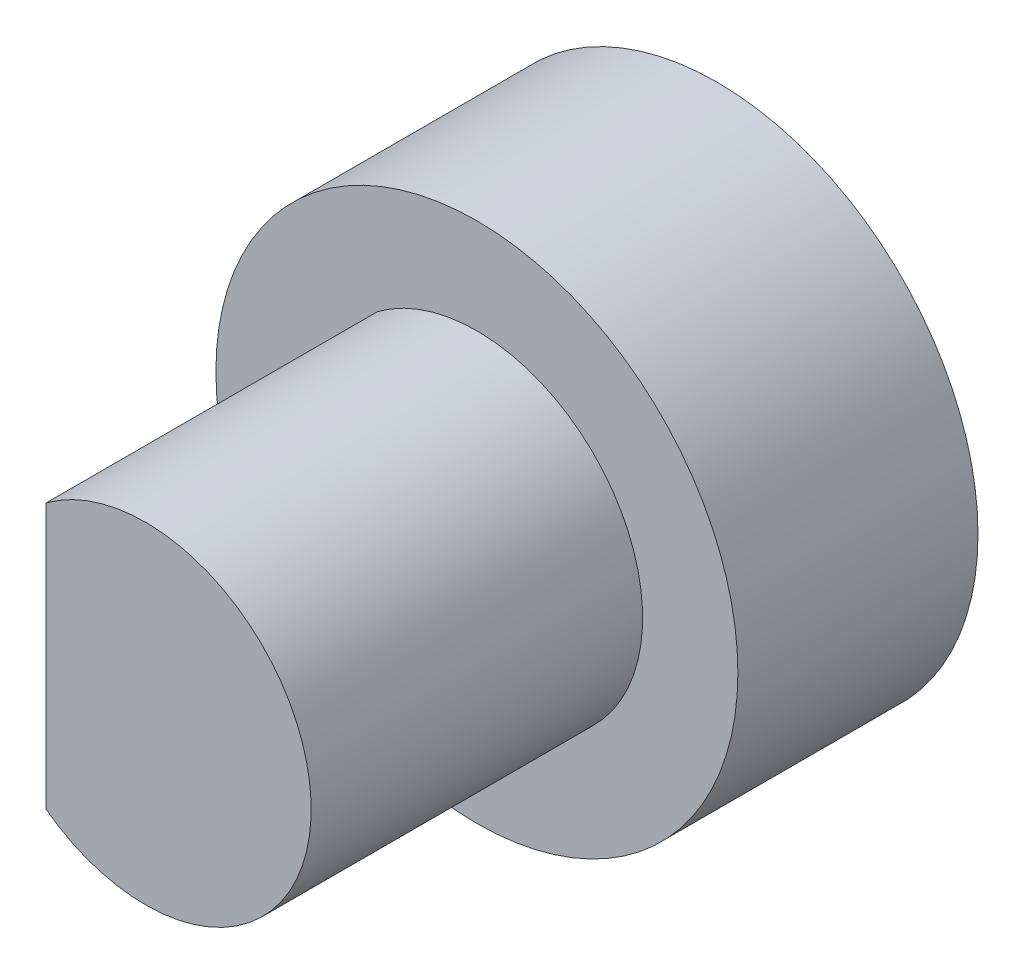
SolidWorks part; units mm, degrees
note: The reader was unsure of these and kept them because the rebuilt part matched: shared geometry of "Sketch9<3>".
ref_plane "Front Plane" through (0, 0, 0) normal (0, 0, 1) x (1, 0, 0)
ref_plane "Top Plane" through (0, 0, 0) normal (0, 1, 0) x (1, 0, 0)
ref_plane "Right Plane" through (0, 0, 0) normal (1, 0, 0) x (0, 0, -1)
sketch "Sketch1" plane through (0, 0, 0) normal (0, 0, 1) x (1, 0, 0)
  circle A0 centre (0, 0) radius 3.175
  dimension "D1" = 6.35
extrude "Boss-Extrude1" add sketch "Sketch1" along normal blind 14 contours A0
sketch "Sketch2" plane through (0, 0, 14) normal (0, 0, 1) x (1, 0, 0)
  line L0 (-1.905, 2.54) -> (-1.905, -2.54)
  circle A0 centre (0, 0) radius 3.175 construction
  arc A2 (-1.905, 2.54) -> (-1.905, -2.54) centre (0, 0) ccw
  dimension "D1" = 1.905
extrude "Cut-Extrude2" cut sketch "Sketch2" against normal blind 6.35
ref_point "Point1"
hole_wizard "#6-32 Tapped Hole1" [suppressed] positions "Sketch3" profile "Sketch5" tap size "#6-32" standard "ANSI Inch"
sketch "Sketch3" plane through (0, 0, 0) normal (0, 0, -1) x (-1, 0, 0)
  point P0 (0, 0)
sketch "Sketch5" plane through (0, 0, 0) normal (1, 0, 0) x (0, 1, 0)
  line L0 (0, 0) -> (0, 8.4627)
  line L1 (0, 8.4627) -> (1.3525, 7.65)
  line L2 (1.3525, 7.65) -> (1.3525, 0)
  line L5 (1.3525, 0) -> (0, 0)
  line L10 (0, 8.4627) -> (-1.3526, 7.65) construction
  line L11 (0, -6.35) -> (0, 107.95) construction
  dimension "Tap Drill Dia." = 2.7051
  dimension "Tap Drill Depth" = 7.65
  dimension "Drill Angle" = 118
cosmetic thread "Hole Thread1" [suppressed] parameters "D1"=6.35, "D2"=3.5052
sketch "Sketch6" plane through (0, 0, 0) normal (0, 0, -1) x (-1, 0, 0)
  circle A0 centre (0, 0) radius 1.3891
  dimension "D1" = 2.7781
extrude "Cut-Extrude3" [suppressed] cut sketch "Sketch6" against normal up to surface (7.65 mm away)
sketch "Sketch7" plane through (0, 0, 0) normal (0, 0, -1) x (-1, 0, 0)
  circle A1 centre (0, 0) radius 3.175
  circle A2 centre (0, 0) radius 3.175
  dimension "D1" = 0
extrude "Cut-Extrude4" cut sketch "Sketch7" against normal offset from surface (3.05 mm away) 10.95 up to face at (0.635, 0, 14)
sketch "Sketch9" plane through (0, 0, 3.05) normal (0, 0, -1) x (-1, 0, 0)
  circle A0 centre (0, 0) radius 5
  circle A1 centre (0, 0) radius 1.3891
  dimension "D1" = 10
  dimension "D2" = 2.7781
extrude "Boss-Extrude2" add sketch "Sketch9" against normal up to surface (4.6 mm away) up to face at (-2.54, 0, 7.65)
extrude "Cut-Extrude5" cut sketch "Sketch9<3>" against normal up to surface (4.6 mm away) contours A1 up to face at (0.635, 0, 7.65)
sketch "Sketch9<3>" plane through (0, 0, 3.05) normal (0, 0, -1) x (-1, 0, 0) same geometry as "Sketch9"
